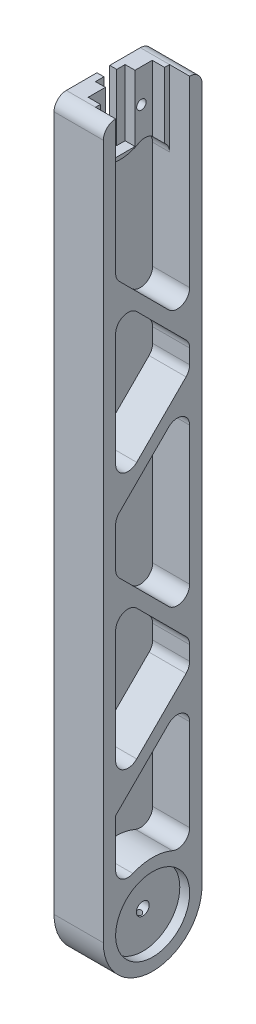
SolidWorks part; units mm, degrees
ref_plane "Front Plane" through (0, 0, 0) normal (0, 0, 1) x (1, 0, 0)
ref_plane "Top Plane" through (0, 0, 0) normal (0, 1, 0) x (1, 0, 0)
ref_plane "Right Plane" through (0, 0, 0) normal (1, 0, 0) x (0, 0, -1)
sketch "Sketch1" plane through (0, 0, 0) normal (0, 1, 0) x (1, 0, 0)
  circle A0 centre (0, 0) radius 12.7
  dimension "D1" = 25.4
extrude "Boss-Extrude1" add sketch "Sketch1" along normal blind 12.7
sketch "Sketch7" plane through (0, 12.7, 0) normal (0, 1, 0) x (1, 0, 0)
  line L0 (-12.7, -9.525) -> (-12.7, 9.525)
  line L1 (-12.7, 9.525) -> (-5.08, 9.525)
  line L2 (-5.08, 9.525) -> (-5.08, 8.255)
  line L5 (-5.08, 8.255) -> (-8.2545, 8.255)
  line L6 (-8.2545, 8.255) -> (-8.2545, -8.255)
  line L7 (-8.2545, -8.255) -> (-5.08, -8.255)
  line L10 (-5.08, -8.255) -> (-5.08, -9.525)
  line L11 (-5.08, -9.525) -> (-12.7, -9.525)
  circle A0 centre (0, 0) radius 12.7 construction
  circle M1 centre (0, 0) radius 12.7
  dimension "D8" = 12.7
  dimension "D2" = 3.1745
  dimension "D3" = 7.62
  dimension "D5" = 16.51
  dimension "D6" = 19.05
  dimension "D7" = 7.62
  dimension "D9" = 1.27
  dimension "D12" = 9.525
extrude "Boss-Extrude2" add sketch "Sketch7" along normal blind 17 contours L11 L10 L7 L6 L5 L2 L1 M1 region at (-9.658, 12.7, 0)
sketch "Sketch8" plane through (0, 29.7, 0) normal (0, 1, 0) x (1, 0, 0)
  line L0 (-8.2545, 8.255) -> (-8.2545, -8.255) construction
  line L1 (-8.2545, 3.81) -> (-10.7945, 3.81)
  line L2 (-8.2545, 3.81) -> (-8.2545, -3.81)
  line L3 (-8.2545, -3.81) -> (-10.7945, -3.81)
  line L4 (-10.7945, 3.81) -> (-10.7945, -3.81)
  line L5 (0, 0) -> (-17.6466, 0) construction
  line L10 (-10.7945, 1.651) -> (-12.7, 1.651)
  line L12 (-10.7945, -1.651) -> (-12.7, -1.651)
  line L13 (-12.7, 1.651) -> (-12.7, -1.651)
  arc A0 (-8.4003, 9.525) -> (-8.4003, -9.525) centre (0, 0) ccw construction
  line M6 (-8.2545, -8.255) -> (-8.2545, 8.255)
  arc M12 (-8.4003, 9.525) -> (-8.4003, -9.525) centre (0, 0) ccw
  dimension "D1" = 7.62
  dimension "D2" = 3.81
  dimension "D3" = 3.302
  dimension "D4" = 1.651
  dimension "D5" = 12.7
  dimension "D6" = 2.54
extrude "Cut-Extrude3" cut sketch "Sketch8" against normal up to surface (17 mm away) contours L4 L5 L12 M12 | L5 L4 L10 M12 | L5 L2 L1 L4 | L5 L4 L3 M6 region at (-9.5245, 29.7, -1.905) region at (-9.5245, 29.7, 1.905) region at (-11.7296, 29.7, -0.8176) region at (-11.7296, 29.7, 0.8176) up to face at (-6.7037, 12.7, 1.1906)
sketch "Sketch13" plane through (0, 29.7, 0) normal (0, 1, 0) x (1, 0, 0)
  line L0 (-12.5922, -9.525) -> (-8.4003, -9.525)
  line L1 (-12.5922, -1.651) -> (-12.5922, -9.525)
  line L2 (-12.5922, 9.525) -> (-8.4003, 9.525)
  line L3 (-12.5922, 1.651) -> (-12.5922, 9.525)
  line L5 (-5.08, -9.525) -> (-8.4003, -9.525) construction
  arc A0 (-8.4003, 9.525) -> (-8.4003, -9.525) centre (0, 0) ccw
  arc A1 (-12.5922, -1.651) -> (-8.4003, -9.525) centre (0, 0) ccw construction
  arc A3 (-8.4003, -9.525) -> (-8.4003, 9.525) centre (0, 0) ccw construction
  arc M10 (-8.4003, 9.525) -> (-12.5922, 1.651) centre (0, 0) ccw
  dimension "D1" = 0
extrude "Boss-Extrude4" add sketch "Sketch13" against normal up to surface (29.7 mm away) contours L3 L2 M10 | A0 L1 L0 region at (-11.3661, 29.7, 7.3819) region at (-11.3661, 29.7, -7.3819) up to face at (0, 0, 12.7)
hole_wizard "#2 Clearance Hole1" positions "Sketch10" profile "Sketch11" hole size "#2" standard "ANSI Inch"
sketch "Sketch10" plane through (-8.2545, 0, 0) normal (1, 0, 0) x (0, 0, -1)
  line L0 (-3.81, 12.7) -> (-8.255, 12.7) construction
  line L1 (8.255, 12.7) -> (3.81, 12.7) construction
  line L2 (12.7, 12.7) -> (-12.7, 12.7) construction
  point P0 (-5.46, 21.2)
  point P2 (5.46, 21.2)
  point P9 (0, 12.7)
  dimension "D1" = 8.5
  dimension "D2" = 8.5
  dimension "D3" = 10.92
  dimension "D4" = 5.46
sketch "Sketch11" plane through (-8.2545, 21.2, 5.46) normal (0, 1, 0) x (0, 0, -1)
  line L0 (0, 0) -> (0, 26.1326)
  line L1 (0, 26.1326) -> (1.2192, 25.4)
  line L2 (1.2192, 25.4) -> (1.2192, 0)
  line L5 (1.2192, 0) -> (0, 0)
  line L10 (0, 26.1326) -> (-1.2192, 25.4) construction
  line L11 (0, -6.35) -> (0, 107.95) construction
  dimension "Hole Dia." = 2.4384
  dimension "Hole Depth" = 25.4
  dimension "Drill Angle" = 118
sketch "Sketch14" plane through (0, 12.7, 0) normal (0, 1, 0) x (1, 0, 0)
  line L1 (26.0577, -24.4231) -> (-26.0577, -24.4231)
  line L2 (26.0577, -24.4231) -> (26.0577, 24.4231)
  line L3 (26.0577, 24.4231) -> (-26.0577, 24.4231)
  line L4 (-26.0577, -24.4231) -> (-26.0577, 24.4231)
  line L5 (26.0577, -24.4231) -> (-26.0577, 24.4231) construction
  line L6 (26.0577, 24.4231) -> (-26.0577, -24.4231) construction
  point P0 (0, 0)
extrude "Cut-Extrude4" cut sketch "Sketch14" against normal up to surface (12.7 mm away) up to face at (-7.6962, 0, 0)
sketch "Sketch15" plane through (0, 12.7, 0) normal (0, -1, 0) x (1, 0, 0)
  line L0 (-5.08, 9.525) -> (-12.5922, 9.525) construction
  line L1 (-12.5922, -12.7) -> (0.1078, -12.7)
  line L2 (-12.5922, -12.7) -> (-12.5922, 12.7)
  line L3 (-12.5922, 12.7) -> (0.1078, 12.7)
  line L4 (0.1078, -12.7) -> (0.1078, 12.7)
  line L5 (-12.5922, -9.525) -> (-12.5922, -1.651) construction
  dimension "D1" = 25.4
  dimension "D2" = 12.7
  dimension "D3" = 3.175
  dimension "D4" = 0
extrude "Boss-Extrude5" add sketch "Sketch15" along normal blind 177.8
sketch "Sketch16" plane through (0, 12.7, 0) normal (0, 1, 0) x (1, 0, 0)
  line L1 (-12.5922, 9.525) -> (0.1078, 9.525)
  line L2 (-12.5922, 9.525) -> (-12.5922, 12.7)
  line L3 (-12.5922, 12.7) -> (0.1078, 12.7)
  line L4 (0.1078, 9.525) -> (0.1078, 12.7)
  line L5 (-12.5922, -9.525) -> (0.1078, -9.525)
  line L6 (-12.5922, -9.525) -> (-12.5922, -12.7)
  line L7 (-12.5922, -12.7) -> (0.1078, -12.7)
  line L8 (0.1078, -9.525) -> (0.1078, -12.7)
extrude "Boss-Extrude6" add sketch "Sketch16" along normal up to surface (17 mm away) up to face at (-9.1803, 29.7, 5.8102)
fillet "Fillet1" radius 3.175 2 edges at (-6.2422, 29.7, 12.7) (-6.2422, 29.7, -12.7)
fillet "Fillet2" radius 12.7 2 edges at (-6.2422, -165.1, 12.7) (-6.2422, -165.1, -12.7)
sketch "Sketch17" plane through (0.1078, 0, 0) normal (1, 0, 0) x (0, 0, -1)
  circle A0 centre (0, -152.4) radius 1.651
  dimension "D1" = 3.302
extrude "Cut-Extrude5" cut sketch "Sketch17" against normal blind 9.525
sketch "Sketch18" plane through (0.1078, 0, 0) normal (1, 0, 0) x (0, 0, -1)
  circle A0 centre (0, -152.4) radius 9.525
  dimension "D1" = 19.05
extrude "Cut-Extrude6" cut sketch "Sketch18" against normal blind 2.54
ref_plane "Plane1" through (0, -152.4, 0) normal (0, 1, 0) x (1, 0, 0)
hole_wizard "#2-56 Tapped Hole1" positions "Sketch20" profile "Sketch19" tap size "#2-56" standard "ANSI Inch"
sketch "Sketch20" plane through (0, -152.4, 0) normal (0, 1, 0) x (1, 0, 0)
  line L0 (-12.5922, 0) -> (0.1078, 0) construction
  point P0 (-3.7022, 0)
  dimension "D1" = 3.81
sketch "Sketch19" plane through (-3.7022, -152.4, 0) normal (1, 0, 0) x (0, 0, 1)
  line L0 (0, 0) -> (0, 13.7422)
  line L1 (0, 13.7422) -> (0.889, 13.208)
  line L2 (0.889, 13.208) -> (0.889, 0)
  line L5 (0.889, 0) -> (0, 0)
  line L10 (0, 13.7422) -> (-0.889, 13.208) construction
  line L11 (0, -6.35) -> (0, 107.95) construction
  dimension "Tap Drill Dia." = 1.778
  dimension "Tap Drill Depth" = 13.208
  dimension "Drill Angle" = 118
sketch "Sketch22" plane through (0.1078, 0, 0) normal (1, 0, 0) x (0, 0, -1)
  line L0 (-12.7, 21.2) -> (12.7, 21.2) construction
  line L1 (-12.7, -152.4) -> (-12.7, 26.525) construction
  line L2 (12.7, -152.4) -> (12.7, 26.525) construction
  line L3 (-9.525, 21.2) -> (-9.525, -152.8792)
  line L4 (9.525, -152.4) -> (9.525, 20.7208)
  line L5 (-9.525, -125.6199) -> (9.525, -106.5699)
  line L6 (-9.525, -121.1297) -> (9.525, -102.0797)
  line L7 (9.525, -95.7297) -> (-9.525, -76.6797)
  line L8 (-9.525, -72.1896) -> (9.525, -91.2396)
  line L9 (-9.525, -59.4896) -> (9.525, -40.4396)
  line L10 (-9.525, -54.9995) -> (9.525, -35.9495)
  line L11 (9.525, -29.5995) -> (-9.525, -10.5495)
  line L12 (-9.525, -6.0593) -> (9.525, -25.1093)
  line L13 (-9.525, -65.8396) -> (9.525, -65.8396) construction
  circle A0 centre (0, -152.4) radius 9.525
  circle A1 centre (0, 21.2) radius 9.525
  circle A2 centre (0, -152.4) radius 12.7
  circle M2 centre (0, -152.4) radius 9.525
  line M8 (9.525, 29.7) -> (9.525, 12.7)
  line M9 (9.525, 12.7) -> (-9.525, 12.7)
  line M10 (-9.525, 12.7) -> (-9.525, 29.7)
  dimension "D1" = 19.05
  dimension "D2" = 19.05
  dimension "D16" = 25.4
  dimension "D3" = 3.175
  dimension "D4" = 3.175
  dimension "D5" = 3.175
  dimension "D6" = 3.175
  dimension "D7" = 6.35
  dimension "D8" = 6.35
  dimension "D9" = 6.35
  dimension "D10" = 45
  dimension "D11" = 6.35
  dimension "D12" = 45
  dimension "D13" = 19.05
  dimension "D14" = 45
  dimension "D15" = 45
extrude "Cut-Extrude7" cut sketch "Sketch22" against normal offset from surface (9.525 mm away) 3.175 contours A1 L3 L12 L4 M9 | A1 M10 M9 | A1 M9 M8 | L4 L11 L3 L10 | L9 L3 L8 L4 | L4 L7 L3 L6 | L5 L3 L4 M2 region at (0.1078, 14.6916, 8.0739) region at (0.1078, -2.1358, -1.0811) region at (0.1078, 14.6916, -8.0739) region at (0.1078, -32.7745, 2.3813) region at (0.1078, -65.8396, -1.905) region at (0.1078, -98.9047, 2.3812) region at (0.1078, -127.9814, -1.2133) up to face at (-12.5922, -25.9178, 0.1501)
sketch "Sketch23" plane through (-8.2545, 0, 0) normal (1, 0, 0) x (0, 0, -1)
  line L1 (6.7829, 16.5373) -> (-6.1899, 16.5373)
  line L2 (6.7829, 16.5373) -> (6.7829, 6.5236)
  line L3 (6.7829, 6.5236) -> (-6.1899, 6.5236)
  line L4 (-6.1899, 16.5373) -> (-6.1899, 6.5236)
extrude "Cut-Extrude8" cut sketch "Sketch23" along normal up to surface (8.3622 mm away) up to face at (0.1078, -128.9724, 0)
fillet "Fillet3" radius 3.175 19 edges at (-7.2486, 21.2, 9.525) (-7.2486, 21.2, -9.525) (-4.6547, -40.4396, -9.525) (-4.6547, -106.5699, -9.525) (-4.6547, -143.9997, 9.525) (-4.6547, -121.1297, 9.525) (-4.6547, -76.6797, 9.525) (-4.6547, -59.4896, 9.525) (-4.6547, -72.1896, 9.525) (-4.6547, -54.9995, 9.525) (-4.6547, -10.5495, 9.525) (-4.6547, -6.0593, 9.525) (-4.6547, -143.9997, -9.525) (-4.6547, -102.0797, -9.525) (-4.6547, -91.2396, -9.525) (-4.6547, -35.9495, -9.525) (-4.6547, -25.1093, -9.525) (-4.6547, -29.5995, -9.525) (-4.6547, -95.7297, -9.525)
sketch "Sketch24" plane through (-12.5922, 0, 0) normal (-1, 0, 0) x (0, 0, 1)
  line L0 (-5.46, 21.2) -> (5.46, 21.2) construction
  circle A0 centre (0, 21.2) radius 12.7
  dimension "D1" = 25.4
